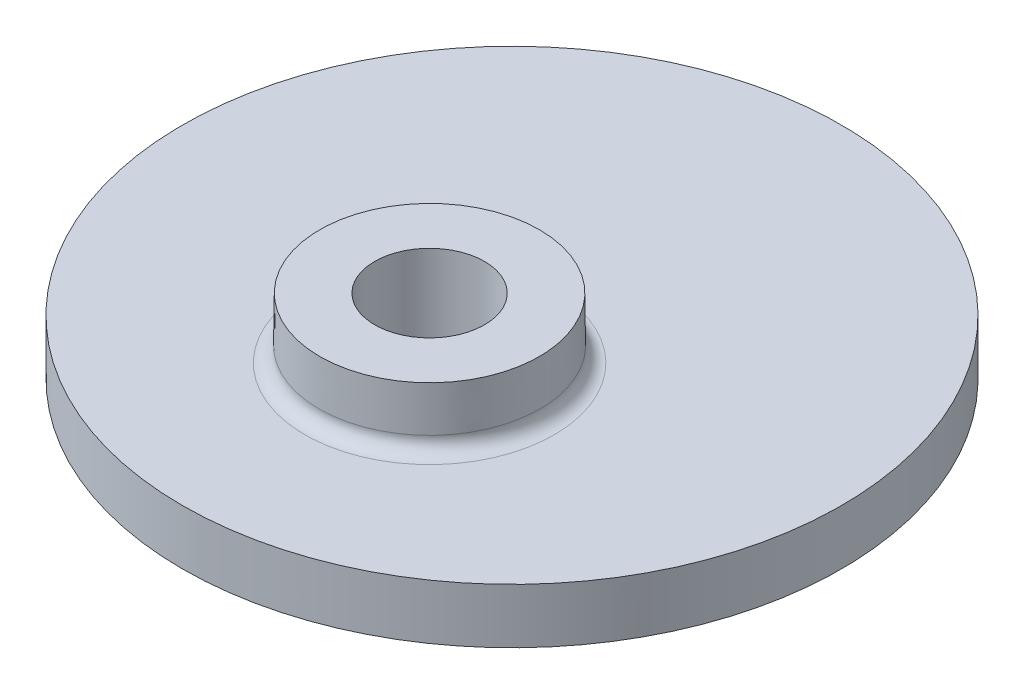
SolidWorks part; units mm, degrees
note: '?' marks a value the reader was unsure of.
ref_plane "Alzado" through (0, 0, 0) normal (0, 0, 1) x (1, 0, 0)
ref_plane "Planta" through (0, 0, 0) normal (0, 1, 0) x (1, 0, 0)
ref_plane "Vista lateral" through (0, 0, 0) normal (1, 0, 0) x (0, 0, -1)
sketch "Croquis1" plane through (0, 0, 0) normal (0, 0, 1) x (1, 0, 0)
  line L0 (0, -587.7846) -> (0, 167.5676) construction
  line L1 (5, 8) -> (10, 8)
  line L2 (10, 8) -> (10.0512, 3.891)
  line L3 (11.348, 2.5) -> (61.3514, 2.5)
  line L4 (61.3514, 2.5) -> (61.3514, -2.5)
  line L5 (61.3514, -2.5) -> (11.3514, -2.5)
  line L6 (10.0514, -3.891) -> (10, -8)
  line L7 (10, -8) -> (5, -8)
  line L8 (5, -8) -> (5, 8)
  arc A0 (10.0512, 3.891) -> (11.348, 2.5) centre (11.348, 3.8) ccw
  arc A1 (11.3514, -2.5) -> (10.0514, -3.891) centre (11.3482, -3.8) ccw
  point P14 (5, 0)
  point P16 (61.3514, 0)
  dimension "D8" = 1.3
  dimension "D9" = 1.3
  dimension "D1" = 50
  dimension "D2" = 5
  dimension "D3" = 5
  dimension "D4" = 5
  dimension "D5" = 5
  dimension "D6" = 8
  dimension "D7" = 8
revolve "Revolución1" add sketch "Croquis1" angle 360 about L0
sketch "Croquis4" plane through (0, 2.5, 0) normal (0, 1, 0) x (1, 0, 0)
  circle A0 centre (0, 7.5) radius 30
  circle A1 centre (0, 0) radius 65
  circle M3 centre (0, 0) radius 61.3514
  dimension "D1" = 60
  dimension "D3" = 130
  dimension "D2" = 7.5
extrude "Cortar-Extruir9" cut sketch "Croquis4" against normal blind 10 flip side to cut contours A0 M3 | A1
ref_axis "Eje1" through (0, -22.9471, 0) along (0, 1, 0)?
